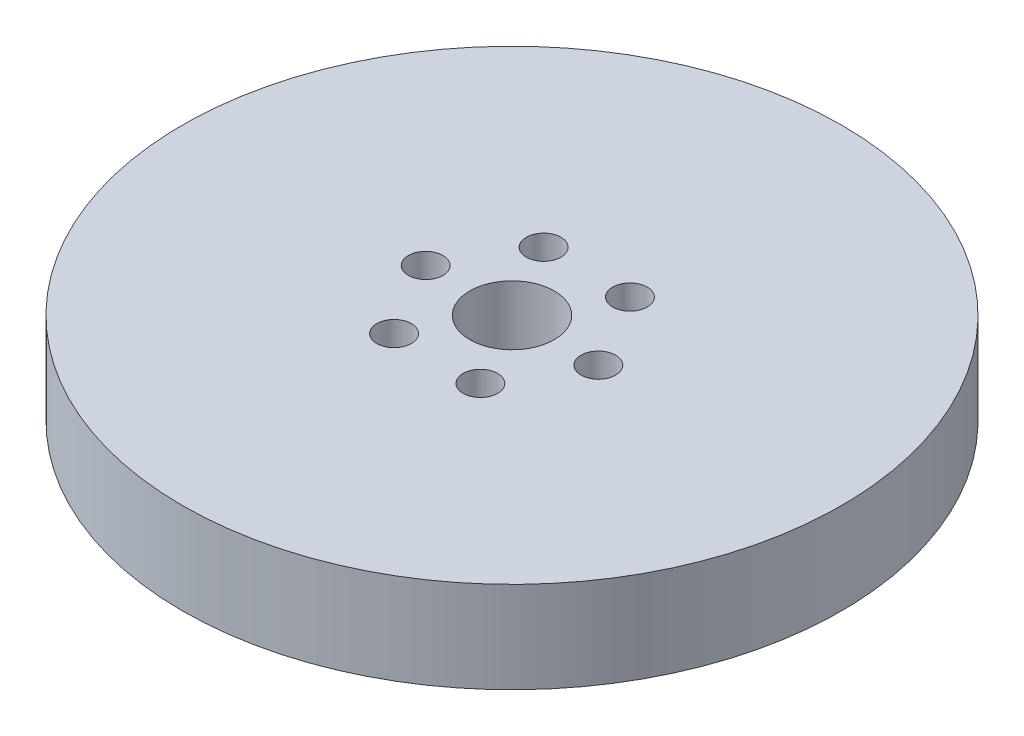
SolidWorks part; units mm, degrees
ref_plane "Front Plane" through (0, 0, 0) normal (0, 0, 1) x (1, 0, 0)
ref_plane "Top Plane" through (0, 0, 0) normal (0, 1, 0) x (1, 0, 0)
ref_plane "Right Plane" through (0, 0, 0) normal (1, 0, 0) x (0, 0, -1)
sketch "Sketch1" plane through (0, 0, 0) normal (0, 1, 0) x (1, 0, 0)
  circle A0 centre (0, 0) radius 97.5
  dimension "FLANGE_OD" = 195
extrude "Boss-Extrude1" add sketch "Sketch1" along normal blind 27
sketch "Sketch2" plane through (0, 0, 0) normal (0, 1, 0) x (1, 0, 0)
  circle A0 centre (0, 0) radius 12.5
  dimension "BORE_D" = 25
extrude "Cut-Extrude1" cut sketch "Sketch2" along normal through all
sketch "Sketch3" plane through (0, 27, 0) normal (0, 1, 0) x (1, 0, 0)
  circle A0 centre (0, 0) radius 25.5422 construction
  circle A1 centre (-25.5422, 0) radius 5.1175
  dimension "BOLT_D" = 10.2351
  dimension "BOLT_PCD" = 51.0843
extrude "Cut-Extrude2" cut sketch "Sketch3" against normal blind 26.7881
pattern_circular "CirPattern1" count 6 over 360 about axis through (0, 0, 0) along (0, 1, 0) of "Cut-Extrude2"
